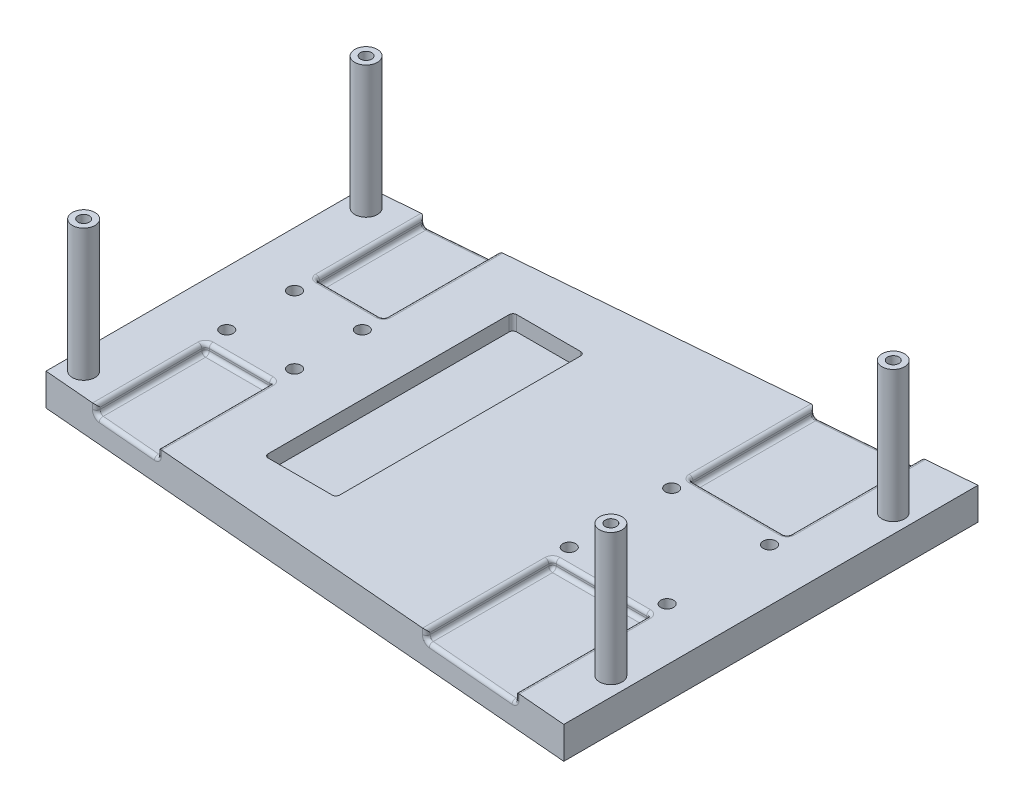
SolidWorks part; units mm, degrees
ref_plane "Front Plane" through (0, 0, 0) normal (0, 0, 1) x (1, 0, 0)
ref_plane "Top Plane" through (0, 0, 0) normal (0, 1, 0) x (1, 0, 0)
ref_plane "Right Plane" through (0, 0, 0) normal (1, 0, 0) x (0, 0, -1)
sketch "Sketch1" plane through (0, 0, 0) normal (0, 1, 0) x (1, 0, 0)
  line L0 (-75, -42.5) -> (-75, 42.5)
  line L1 (-75, -42.5) -> (75, -55)
  line L2 (75, -55) -> (75, 55)
  line L3 (75, 55) -> (-75, 42.5)
  dimension "D1" = 85
  dimension "D2" = 110
  dimension "D3" = 150
  dimension "D4" = 75
  dimension "D5" = 42.5
extrude "Boss-Extrude1" add sketch "Sketch1" along normal blind 8.5
sketch "Sketch2" plane through (0, 8.5, 0) normal (0, 1, 0) x (1, 0, 0)
  line L0 (35, -13.55) -> (61, -13.55) construction
  line L1 (61, -13.55) -> (61, 13.65) construction
  line L2 (61, 13.65) -> (35, 13.65) construction
  line L3 (35, 13.65) -> (35, -13.55) construction
  line L4 (-60.5, -9) -> (-60.5, 9) construction
  line L5 (-60.5, 9) -> (-42.5, 9) construction
  line L6 (-42.5, 9) -> (-42.5, -9) construction
  line L7 (-42.5, -9) -> (-60.5, -9) construction
  circle A0 centre (35, -13.55) radius 3
  circle A1 centre (35, 13.65) radius 3
  circle A2 centre (61, 13.65) radius 3
  circle A3 centre (61, -13.55) radius 3
  circle A4 centre (-60.5, -9) radius 3
  circle A5 centre (-60.5, 9) radius 3
  circle A6 centre (-42.5, 9) radius 3
  circle A7 centre (-42.5, -9) radius 3
  dimension "D2" = 6
  dimension "D3" = 6
  dimension "D4" = 6
  dimension "D5" = 6
  dimension "D11" = 6
  dimension "D12" = 6
  dimension "D13" = 6
  dimension "D14" = 6
  dimension "D1" = 13.55
  dimension "D6" = 27.2
  dimension "D7" = 26
  dimension "D8" = 35
  dimension "D9" = 18
  dimension "D10" = 18
  dimension "D15" = 42.5
  dimension "D16" = 9
hole_wizard "Ø3.0mm Dowel Hole2" positions "Sketch3" profile "Sketch4" hole size "Ø3.0" standard "ANSI Metric" end condition through all
sketch "Sketch3" plane through (0, 8.5, 0) normal (0, 1, 0) x (1, 0, 0)
  point P0 (-60.5, -9)
  point P3 (-60.5, 9)
  point P6 (-42.5, 9)
  point P9 (-42.5, -9)
  point P12 (35, -13.55)
  point P15 (35, 13.65)
  point P18 (61, 13.65)
  point P21 (61, -13.55)
sketch "Sketch4" plane through (-60.5, 8.5, 9) normal (1, 0, 0) x (0, 0, 1)
  line L0 (0, 0) -> (0, 8.5)
  line L1 (0, 8.5) -> (1.5, 8.5)
  line L2 (1.5, 8.5) -> (1.5, 0)
  line L5 (1.5, 0) -> (0, 0)
  line L11 (0, -6.35) -> (0, 107.95) construction
  dimension "Thru Hole Dia." = 3
  dimension "Thru Hole Depth" = 8.5
sketch "Sketch5" plane through (0, 8.5, 0) normal (0, 1, 0) x (1, 0, 0)
  line L0 (70, -37.5) -> (-70, -37.5) construction
  line L1 (-70, -37.5) -> (-70, 37.5) construction
  line L2 (-70, 37.5) -> (70, 37.5) construction
  line L3 (70, 37.5) -> (70, -37.5) construction
  circle A0 centre (70, 37.5) radius 3
  circle A1 centre (70, -37.5) radius 3
  circle A2 centre (-70, -37.5) radius 3
  circle A3 centre (-70, 37.5) radius 3
  dimension "D3" = 6
  dimension "D4" = 6
  dimension "D5" = 6
  dimension "D6" = 6
  dimension "D1" = 140
  dimension "D2" = 75
  dimension "D7" = 37.5
  dimension "D8" = 70
extrude "Boss-Extrude2" add sketch "Sketch5" along normal blind 35
hole_wizard "Ø3.0mm Dowel Hole1" positions "Sketch6" profile "Sketch8" hole size "Ø3.0" standard "ANSI Metric"
sketch "Sketch6" plane through (0, 43.5, 0) normal (0, 1, 0) x (1, 0, 0)
  point P0 (-70, -37.5)
  point P3 (-70, 37.5)
  point P6 (70, 37.5)
  point P9 (70, -37.5)
sketch "Sketch8" plane through (-70, 43.5, 37.5) normal (1, 0, 0) x (0, 0, 1)
  line L0 (0, 0) -> (0, 15.9013)
  line L1 (0, 15.9013) -> (1.5, 15)
  line L2 (1.5, 15) -> (1.5, 0)
  line L5 (1.5, 0) -> (0, 0)
  line L10 (0, 15.9013) -> (-1.5, 15) construction
  line L11 (0, -6.35) -> (0, 107.95) construction
  dimension "Hole Dia." = 3
  dimension "Hole Depth" = 15
  dimension "Drill Angle" = 118
hole_wizard "CSK for M3 Flat Head Machine Screw1" positions "Sketch9" profile "Sketch10" countersink size "M3" standard "ANSI Metric" end condition through all
sketch "Sketch9" plane through (0, 0, 0) normal (0, -1, 0) x (-1, 0, 0)
  point P0 (42.5, 9)
  point P3 (60.5, -9)
  point P6 (60.5, 9)
  point P9 (42.5, -9)
  point P12 (-35, 13.65)
  point P15 (-35, -13.55)
  point P18 (-61, -13.55)
  point P21 (-61, 13.65)
sketch "Sketch10" plane through (-42.5, 0, -9) normal (1, 0, 0) x (0, 0, -1)
  line L0 (0, 0) -> (0, 43.5)
  line L1 (0, 43.5) -> (1.7, 43.5)
  line L2 (1.7, 43.5) -> (1.7, 1.45)
  line L3 (1.7, 1.45) -> (3.15, 0)
  line L5 (3.15, 0) -> (0, 0)
  line L6 (-1.7, 1.45) -> (-3.15, 0) construction
  line L11 (0, -6.35) -> (0, 107.95) construction
  dimension "Thru Hole Dia." = 3.4
  dimension "Thru Hole Depth" = 43.5
  dimension "Near C'Sink Dia." = 6.3
  dimension "Near C'Sink Angle" = 90
sketch "Sketch11" plane through (0, 8.5, 0) normal (0, 1, 0) x (1, 0, 0)
  line L0 (62.7, 13.65) -> (33.3, 13.65) construction
  line L1 (33.3, 13.65) -> (48.8898, 52.8242) construction
  line L2 (75, 55) -> (-75, 42.5) construction
  line L3 (48.8898, 52.8242) -> (62.7, 13.65) construction
  line L4 (62.7, -13.55) -> (33.3, -13.55) construction
  line L5 (33.3, -13.55) -> (48.8916, -52.8243) construction
  line L6 (-75, -42.5) -> (75, -55) construction
  line L7 (48.8916, -52.8243) -> (62.7, -13.55) construction
  line L8 (61.1031, -18.0919) -> (35.1031, -18.0919)
  line L9 (61.1029, 18.1803) -> (35.1029, 18.1803)
  line L10 (35.1031, -18.0919) -> (48.8916, -52.8243) construction
  line L11 (48.8916, -52.8243) -> (61.1031, -18.0919) construction
  line L12 (61.1029, 18.1803) -> (48.8898, 52.8242) construction
  line L13 (48.8898, 52.8242) -> (35.1029, 18.1803) construction
  line L14 (-40.8, 9) -> (-62.2, 9) construction
  line L15 (-62.2, 9) -> (-51.5, 44.4583) construction
  line L16 (-51.5, 44.4583) -> (-40.8, 9) construction
  line L17 (-40.8, -9) -> (-62.2, -9) construction
  line L20 (-40.8, -9) -> (-51.5, -44.4583) construction
  line L21 (-42.5, 14.6336) -> (-60.5, 14.6336)
  line L22 (-60.5, -14.6336) -> (-42.5, -14.6336)
  line L23 (-51.5, -44.4583) -> (-62.2, -9) construction
  line L24 (-42.5, -14.6336) -> (-51.5, -44.4583) construction
  line L25 (-51.5, -44.4583) -> (-60.5, -14.6336) construction
  line L26 (-51.5, 44.4583) -> (-42.5, 14.6336) construction
  line L27 (-60.5, 14.6336) -> (-51.5, 44.4583) construction
  line L28 (-42.5, 14.6336) -> (-42.5, 45.2083)
  line L29 (-60.5, 14.6336) -> (-60.5009, 43.7083)
  line L30 (-42.5, 45.2083) -> (-60.5009, 43.7083)
  line L31 (-60.5, -14.6336) -> (-60.5, -43.7083)
  line L32 (-42.5, -14.6336) -> (-42.5, -45.2083)
  line L33 (-42.5, -45.2083) -> (-60.5, -43.7083)
  line L34 (61.1029, 18.1803) -> (61.1071, 53.8423)
  line L35 (35.1029, 18.1803) -> (35.1036, 51.6753)
  line L36 (35.1036, 51.6753) -> (61.1071, 53.8423)
  line L37 (61.1031, -18.0919) -> (61.1031, -53.8419)
  line L38 (35.1031, -18.0919) -> (35.1031, -51.6753)
  line L39 (61.1031, -53.8419) -> (35.1031, -51.6753)
  circle A0 centre (61, 13.65) radius 1.7 construction
  circle A1 centre (35, 13.65) radius 1.7 construction
  circle A2 centre (61, -13.55) radius 1.7 construction
  circle A3 centre (35, -13.55) radius 1.7 construction
  circle A4 centre (-42.5, 9) radius 1.7 construction
  circle A5 centre (-60.5, 9) radius 1.7 construction
  circle A6 centre (-42.5, -9) radius 1.7 construction
  circle A7 centre (-60.5, -9) radius 1.7 construction
  point P50 (50.9652, 53.1667)
  point P53 (-47.9932, 44.7506)
  point P54 (-47.9932, -44.7506)
  point P55 (46.9834, 52.6653)
  point P56 (41.7921, -52.2327)
  point P57 (38.3, -51.9414)
  point P58 (46.9834, -52.6653)
  point P59 (-46.2878, 44.8927)
  point P60 (-46.2878, -44.8927)
  point P61 (42.3166, -52.2764)
  point P62 (42.3166, 52.2763)
  point P63 (-42.5, -45.2083)
  point P64 (-60.5, -43.7083)
  point P65 (-60.5, 43.7083)
  point P66 (-42.5, 45.2083)
  point P67 (66, 54.25)
  point P68 (66, -54.25)
  point P69 (35.1031, -51.6753)
  point P70 (61.1031, -53.8419)
  point P71 (61.1029, 53.8423)
  point P72 (35.1029, 51.6753)
  dimension "D1" = 26
  dimension "D2" = 26
  dimension "D3" = 42.256
  dimension "D4" = 42.1623
  dimension "D5" = 18
  dimension "D6" = 18
  dimension "D7" = 37.0376
  dimension "D8" = 37.0376
  dimension "D9" = 35.6619
  dimension "D10" = 33.495
  dimension "D11" = 33.5833
  dimension "D12" = 35.75
  dimension "D13" = 30.5748
  dimension "D14" = 30.5748
  dimension "D15" = 29.0747
  dimension "D16" = 29.0748
extrude "Cut-Extrude1" cut sketch "Sketch11" against normal blind 2.5
fillet "Fillet2" radius 1 10 edges at (-51.5, 8.5, -14.6336) (-51.5004, 6, -44.4583) (-60.5009, 7.25, -43.7083) (-60.5004, 6, -29.1709) (-60.5, 7.25, -14.6336) (-60.5004, 8.5, -29.1709) (-42.5, 7.25, -14.6336) (-42.5, 6, -29.921) (-42.5, 7.25, -45.2083) (-42.5, 8.5, -29.921)
fillet "Fillet3" radius 1 11 edges at (-51.5, 6, 44.4583) (-60.5, 6, 29.171) (-60.5, 7.25, 43.7083) (-60.5, 8.5, 29.171) (-51.5, 6, 14.6336) (-60.5, 7.25, 14.6336) (-51.5, 8.5, 14.6336) (-42.5, 7.25, 45.2083) (-42.5, 6, 29.921) (-42.5, 7.25, 14.6336) (-42.5, 8.5, 29.921)
fillet "Fillet4" radius 1 11 edges at (48.1054, 6, -52.7588) (48.1029, 8.5, -18.1803) (35.1036, 7.25, -51.6753) (35.1032, 6, -34.9278) (35.1029, 7.25, -18.1803) (35.1032, 8.5, -34.9278) (48.1029, 6, -18.1803) (61.1029, 7.25, -18.1803) (61.105, 6, -36.0113) (61.1071, 7.25, -53.8423) (61.105, 8.5, -36.0113)
fillet "Fillet5" radius 1 11 edges at (48.1031, 6, 52.7586) (35.1031, 6, 34.8836) (35.1031, 7.25, 51.6753) (35.1031, 8.5, 34.8836) (61.1031, 7.25, 53.8419) (61.1031, 6, 35.9669) (61.1031, 8.5, 35.9669) (61.1031, 7.25, 18.0919) (48.1031, 6, 18.0919) (35.1031, 7.25, 18.0919) (48.1031, 8.5, 18.0919)
sketch "Sketch12" plane through (0, 8.5, 0) normal (0, 1, 0) x (1, 0, 0)
  line L0 (75, -55) -> (75, 55) construction
  line L1 (-25.5, 33) -> (-8.5, 33)
  line L2 (-26.5, 32) -> (-26.5, -32)
  line L3 (-25.5, -33) -> (-8.5, -33)
  line L4 (-7.5, 32) -> (-7.5, -32)
  arc A0 (-8.5, -33) -> (-7.5, -32) centre (-8.5, -32) ccw
  arc A1 (-26.5, -32) -> (-25.5, -33) centre (-25.5, -32) ccw
  arc A2 (-25.5, 33) -> (-26.5, 32) centre (-25.5, 32) ccw
  arc A3 (-8.5, 33) -> (-7.5, 32) centre (-8.5, 32) cw
  point P6 (75, 0)
  point P9 (-7.5, -33)
  point P12 (-26.5, -33)
  point P17 (-7.5, 33)
  dimension "D5" = 1
  dimension "D1" = 66
  dimension "D2" = 19
  dimension "D3" = 33
  dimension "D4" = 82.5
extrude "Cut-Extrude2" cut sketch "Sketch12" against normal blind 4 contours L2 A1 L3 A0 L4 A3 L1 A2
